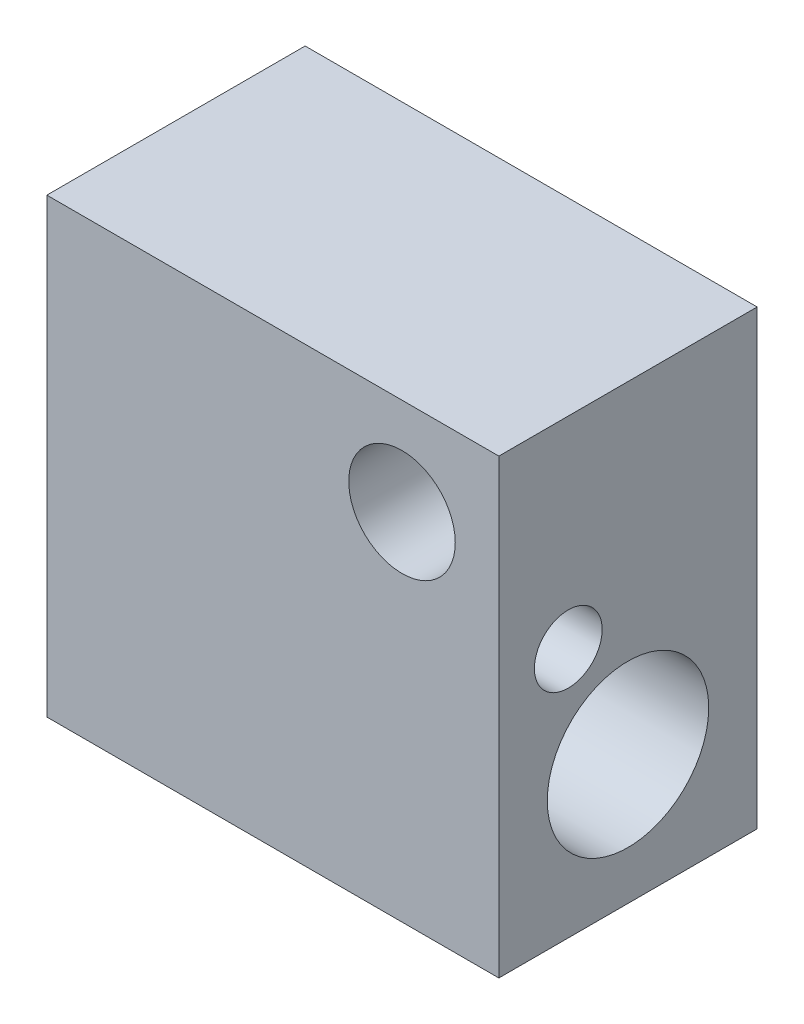
SolidWorks part; units mm, degrees
material "6061 Alloy"
ref_plane "Front Plane" through (0, 0, 0) normal (0, 0, 1) x (1, 0, 0)
ref_plane "Top Plane" through (0, 0, 0) normal (0, 1, 0) x (1, 0, 0)
ref_plane "Right Plane" through (0, 0, 0) normal (1, 0, 0) x (0, 0, -1)
sketch "Sketch1" plane through (0, 0, 0) normal (0, 0, 1) x (1, 0, 0)
  line L1 (0, 0) -> (14, 0)
  line L2 (0, 0) -> (0, 14)
  line L3 (0, 14) -> (14, 14)
  line L4 (14, 0) -> (14, 14)
  dimension "D1" = 14
  dimension "D2" = 14
extrude "Boss-Extrude1" add sketch "Sketch1" along normal blind 8
hole_wizard "M4x0.7 Tapped Hole1" positions "Sketch3" profile "Sketch2" tap size "M4x0.7" standard "BSI" end condition through all
sketch "Sketch3" plane through (0, 0, 8) normal (0, 0, 1) x (1, 0, 0)
  line L0 (14, 0) -> (14, 14) construction
  line L1 (14, 14) -> (0, 14) construction
  point P0 (11, 11)
  dimension "7" = 3
  dimension "D2" = 3
sketch "Sketch2" plane through (11, 11, 8) normal (1, 0, 0) x (0, -1, 0)
  line L0 (0, 0) -> (0, 8)
  line L1 (0, 8) -> (1.65, 8)
  line L2 (1.65, 8) -> (1.65, 0)
  line L5 (1.65, 0) -> (0, 0)
  line L11 (0, -6.35) -> (0, 107.95) construction
  dimension "Thru Tap Drill Dia." = 3.3
  dimension "Thru Tap Drill Depth" = 8
cosmetic thread "Hole Thread1"
ref_axis "Axis1" through (11, 11, 0) along (0, 0, 1)
hole_wizard "Ø5.0 (5) Diameter Hole1" positions "Sketch5" profile "Sketch4" hole size "Ø5.0" standard "Ansi Metric" end condition through all
sketch "Sketch5" plane through (0, 0, 0) normal (-1, 0, 0) x (0, 0, 1)
  line L0 (4, 0) -> (4, 7.9761) construction
  line L1 (8, 0) -> (0, 0) construction
  point P0 (4, 4)
  dimension "D1" = 4
sketch "Sketch4" plane through (0, 4, 4) normal (0, 1, 0) x (0, 0, 1)
  line L0 (0, 0) -> (0, 14)
  line L1 (0, 14) -> (2.5, 14)
  line L2 (2.5, 14) -> (2.5, 0)
  line L5 (2.5, 0) -> (0, 0)
  line L11 (0, -6.35) -> (0, 107.95) construction
  dimension "Thru Hole Dia." = 5
  dimension "Thru Hole Depth" = 14
hole_wizard "Ø2.1 (2.1) Diameter Hole1" positions "Sketch9" profile "Sketch8" hole size "Ø2.1" standard "Ansi Metric" end condition through all
sketch "Sketch9" plane through (0, 0, 0) normal (-1, 0, 0) x (0, 0, 1)
  line L0 (4, 14) -> (4, 0) construction
  line L1 (8, 14) -> (0, 14) construction
  line L3 (8, 0) -> (0, 0) construction
  line L5 (0, 14) -> (0, 0) construction
  point P0 (5.85, 7.75)
  dimension "D1" = 6.25
  dimension "D2" = 5.85
sketch "Sketch8" plane through (0, 7.75, 5.85) normal (0, 1, 0) x (0, 0, 1)
  line L0 (0, 0) -> (0, 14)
  line L1 (0, 14) -> (1.05, 14)
  line L2 (1.05, 14) -> (1.05, 0)
  line L5 (1.05, 0) -> (0, 0)
  line L11 (0, -6.35) -> (0, 107.95) construction
  dimension "Thru Hole Dia." = 2.1
  dimension "Thru Hole Depth" = 14
ref_plane "Plane1" through (0, 0, 4) normal (0, 0, 1) x (1, 0, 0)
hole_wizard "Ø4.0 (4) Diameter Hole1" positions "3DSketch4" profile "Sketch13" hole size "Ø4.0" standard "ANSI Metric"
sketch3d "3DSketch4"
  circle A0 centre (11, 11, 0) radius 1.65 construction
  point P0 (11, 11, 0)
  point P6 (11, 11, 1.65)
sketch "Sketch13" plane through (11, 11, 0) normal (1, 0, 0) x (0, 1, 0)
  line L0 (0, 0) -> (0, 2.2017)
  line L1 (0, 2.2017) -> (2, 1)
  line L2 (2, 1) -> (2, 0)
  line L5 (2, 0) -> (0, 0)
  line L10 (0, 2.2017) -> (-2, 1) construction
  line L11 (0, -6.35) -> (0, 107.95) construction
  dimension "Hole Dia." = 4
  dimension "Hole Depth" = 1
  dimension "Drill Angle" = 118
